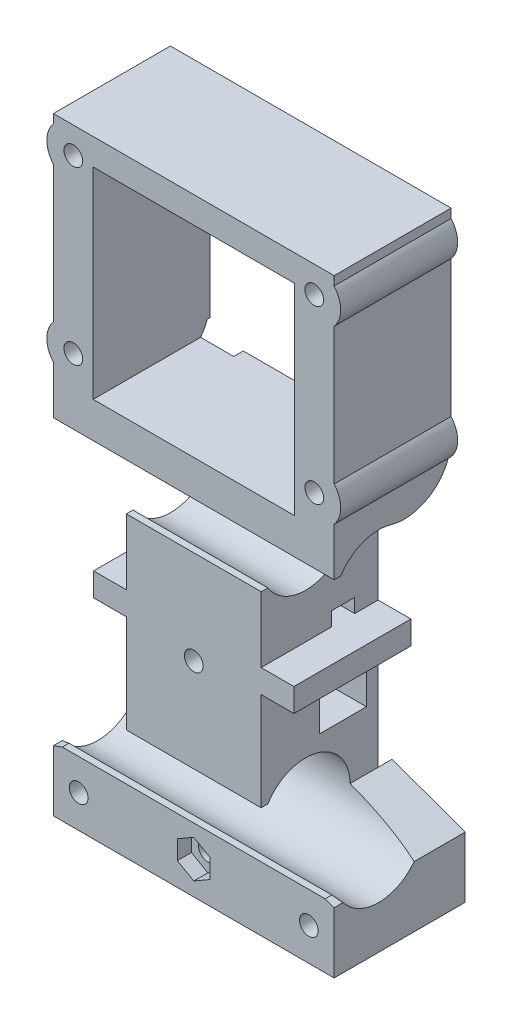
SolidWorks part; units mm, degrees
material "ABS"
ref_plane "Спереди" through (0, 0, 0) normal (0, 0, 1) x (1, 0, 0)
ref_plane "Сверху" through (0, 0, 0) normal (0, 1, 0) x (1, 0, 0)
ref_plane "Справа" through (0, 0, 0) normal (1, 0, 0) x (0, 0, -1)
sketch "Эскиз1" plane through (0, 0, 0) normal (0, 0, 1) x (1, 0, 0)
  line L1 (30, -65) -> (-30, -65)
  line L2 (30, -65) -> (30, 65)
  line L3 (30, 65) -> (-30, 65)
  line L4 (-30, -65) -> (-30, 65)
  line L5 (30, -65) -> (-30, 65) construction
  line L6 (30, 65) -> (-30, -65) construction
  point P0 (0, 0)
  dimension "D1" = 60
  dimension "D2" = 130
extrude "Бобышка-Вытянуть1" add sketch "Эскиз1" along normal blind 25
sketch "Эскиз2" plane through (0, 0, 0) normal (0, 0, -1) x (-1, 0, 0)
  line L0 (-30, 3.7) -> (-14.4, 3.7)
  line L1 (21.5, 16.35) -> (-21.5, 16.35)
  line L2 (21.5, 16.35) -> (21.5, 59.35)
  line L3 (21.5, 59.35) -> (-21.5, 59.35)
  line L4 (-21.5, 16.35) -> (-21.5, 59.35)
  line L5 (21.5, 16.35) -> (-21.5, 59.35) construction
  line L6 (21.5, 59.35) -> (-21.5, 16.35) construction
  line L7 (-30, -65) -> (-30, 65) construction
  line L8 (-14.4, -5.8) -> (-14.4, 13.2) construction
  line L9 (-14.4, 3.7) -> (-14.4, -46.3)
  line L10 (-14.4, -36.8) -> (-14.4, -55.8) construction
  line L11 (-14.4, -46.3) -> (-30, -52)
  line L12 (-30, -52) -> (-30, 3.7)
  line L13 (14.4, -46.3) -> (30, -52)
  line L14 (0, 16.35) -> (0, -65) construction
  line L15 (30, -65) -> (-30, -65) construction
  line L16 (14.4, 3.7) -> (14.4, -46.3)
  line L17 (30, 3.7) -> (14.4, 3.7)
  line L18 (30, -52) -> (30, 3.7)
  line L19 (-30, -65) -> (-30, 15) construction
  point P0 (0, 37.85)
  dimension "D1" = 43
  dimension "D3" = 13
extrude "Вырез-Вытянуть1" cut sketch "Эскиз2" against normal through all
sketch "Эскиз3" plane through (-30, 0, 0) normal (-1, 0, 0) x (0, 0, 1)
  line L0 (15.5, -5.8) -> (15.5, -36.9) construction
  line L1 (23.5777, 8.7) -> (25, 8.7)
  line L2 (6, -29.85) -> (25, -29.85) construction
  line L3 (6, -29.85) -> (6, -12.85) construction
  line L4 (6, -12.85) -> (25, -12.85) construction
  line L5 (25, -29.85) -> (25, -12.85) construction
  line L6 (6, -29.85) -> (25, -12.85) construction
  line L7 (6, -12.85) -> (25, -29.85) construction
  line L8 (2.5, -33.85) -> (12.5, -33.85)
  line L9 (2.5, -33.85) -> (2.5, -25.85)
  line L10 (2.5, -25.85) -> (12.5, -25.85)
  line L11 (12.5, -33.85) -> (12.5, -25.85)
  line L12 (2.5, -33.85) -> (12.5, -25.85) construction
  line L13 (2.5, -25.85) -> (12.5, -33.85) construction
  line L14 (25, 3.7) -> (25, 65) construction
  line L15 (25, 8.7) -> (25, 3.7)
  line L16 (25, -46.3) -> (25, 3.7) construction
  line L17 (25, -1.3) -> (23.5777, -1.3)
  line L18 (25, 8.7) -> (25, 3.7)
  line L19 (25, 3.7) -> (25, -1.3)
  line L20 (25, -1.3) -> (25, 3.7)
  line L21 (23.5777, -41.3) -> (25, -41.3)
  line L22 (25, -41.3) -> (25, -46.3)
  line L23 (25, -46.3) -> (25, -51.3)
  line L24 (25, -65) -> (25, -52) construction
  line L25 (25, -51.3) -> (23.5777, -51.3)
  line L26 (25, -65) -> (25, 15) construction
  arc A0 (23.5777, -41.3) -> (23.5777, -51.3) centre (15.5, -46.3) ccw
  arc A1 (23.5777, 8.7) -> (23.5777, -1.3) centre (15.5, 3.7) ccw
  circle A2 centre (15.5, 3.7) radius 9.5 construction
  circle A3 centre (15.5, -46.3) radius 9.4 construction
  point P4 (25, -46.3)
  point P13 (15.5, -21.35)
  point P18 (7.5, -29.85)
  point P34 (25, 3.7)
  line M2 (25, -52) -> (0, -52)
  dimension "D1" = 19
  dimension "D2" = 17
  dimension "D3" = 10
  dimension "D4" = 8
  dimension "D5" = 5
  dimension "D6" = 17.5
extrude "Вырез-Вытянуть2" cut sketch "Эскиз3" against normal through all contours L1 A1 L17 L19 L15 | L21 A0 L25 L23 L22 M2 | L8 L11 L10 L9 | A0 M2 region at (-30, 3.7, 15.6446) region at (-30, -29.85, 7.5) region at (-30, -45.1188, 15.6682) region at (-30, -53.5495, 15.5)
fillet "Скругление1" radius 20 2 edges at (-22.2, 3.7, 0) (22.2, 3.7, 0)
fillet "Скругление2" radius 10 2 edges at (-22.2, 3.7, 6) (22.2, 3.7, 6)
sketch "Эскиз4" plane through (0, 0, 0) normal (0, 0, -1) x (-1, 0, 0)
  line L0 (0, -1.3) -> (0, -41.3) construction
  line L1 (-14.4, -1.3) -> (14.4, -1.3) construction
  line L2 (-14.4, -41.3) -> (14.4, -41.3) construction
  line L3 (-30, 8.7) -> (30, 8.7) construction
  line L4 (30, 12.4083) -> (30, 22.4083) construction
  line L5 (21.5, 59.35) -> (-21.5, 59.35) construction
  circle A0 centre (-24.6, -58) radius 2
  circle A1 centre (24.6, -58) radius 2
  circle A2 centre (0, -21.3) radius 2
  circle A3 centre (-25.75, 22.7) radius 2
  circle A4 centre (25.75, 22.7) radius 2
  circle A5 centre (-24.6, -58) radius 2 construction
  circle A6 centre (25.75, 59.35) radius 2
  circle A7 centre (-25.75, 59.35) radius 2
  dimension "D1" = 14
  dimension "D2" = 4.25
extrude "Вырез-Вытянуть3" cut sketch "Эскиз4" against normal through all
sketch "Эскиз5" plane through (0, 0, 0) normal (0, 0, -1) x (-1, 0, 0)
  circle A0 centre (25.75, 22.7) radius 4.25
  circle A1 centre (-25.75, 22.7) radius 4.25
  circle A2 centre (-25.75, 22.7) radius 2
  circle A3 centre (25.75, 22.7) radius 2
  circle A4 centre (0, -21.3) radius 2 construction
  dimension "D1" = 8.5
extrude "Бобышка-Вытянуть2" add sketch "Эскиз5" against normal through all
sketch "Эскиз6" plane through (0, 0, 0) normal (0, 0, -1) x (-1, 0, 0)
  line L0 (-30, 65) -> (30, 65) construction
  line L1 (-21.5, 26.4229) -> (-21.5, 18.9771)
  line L2 (21.5, 59.35) -> (20.1, 59.35)
  line L3 (21.5, 59.35) -> (21.5, 55.6271)
  line L5 (-21.5, 59.35) -> (-21.5, 55.6271)
  line L7 (-21.5, 59.35) -> (-21.5, 22.4083) construction
  line L8 (-20.1, 59.35) -> (-21.5, 59.35)
  line L9 (21.5, 26.4229) -> (21.5, 18.9771)
  arc A0 (-20.1, 59.35) -> (-21.5, 55.6271) centre (-25.75, 59.35) ccw
  arc A1 (21.5, 55.6271) -> (20.1, 59.35) centre (25.75, 59.35) ccw
  arc A2 (21.5, 18.9771) -> (21.5, 26.4229) centre (25.75, 22.7) ccw
  arc A3 (-21.5, 26.4229) -> (-21.5, 18.9771) centre (-25.75, 22.7) ccw
  circle A4 centre (-25.75, 59.35) radius 2
  circle A5 centre (-25.75, 22.7) radius 2
  circle A6 centre (25.75, 59.35) radius 2
  circle A7 centre (25.75, 22.7) radius 2
  circle A8 centre (25.75, 22.7) radius 2 construction
extrude "Бобышка-Вытянуть3" add sketch "Эскиз6" against normal up to surface (25 mm away) up to face at (0, 37.85, 25)
sketch "Эскиз7" plane through (0, 0, 0) normal (0, 0, -1) x (-1, 0, 0)
  line L0 (30, -52) -> (30, -65) construction
  line L1 (0, -17.2585) -> (-3.5, -19.2793)
  line L2 (-3.5, -19.2793) -> (-3.5, -23.3207)
  line L3 (-3.5, -23.3207) -> (0, -25.3415)
  line L4 (0, -25.3415) -> (3.5, -23.3207)
  line L5 (3.5, -23.3207) -> (3.5, -19.2793)
  line L6 (3.5, -19.2793) -> (0, -17.2585)
  line L7 (-24.6, -53.9585) -> (-28.1, -55.9793)
  line L8 (-28.1, -55.9793) -> (-28.1, -60.0207)
  line L9 (-28.1, -60.0207) -> (-24.6, -62.0415)
  line L10 (-24.6, -62.0415) -> (-21.1, -60.0207)
  line L11 (-21.1, -60.0207) -> (-21.1, -55.9793)
  line L12 (-21.1, -55.9793) -> (-24.6, -53.9585)
  line L13 (24.6, -53.9585) -> (21.1, -55.9793)
  line L14 (21.1, -55.9793) -> (21.1, -60.0207)
  line L15 (21.1, -60.0207) -> (24.6, -62.0415)
  line L16 (24.6, -62.0415) -> (28.1, -60.0207)
  line L17 (28.1, -60.0207) -> (28.1, -55.9793)
  line L18 (28.1, -55.9793) -> (24.6, -53.9585)
  circle A0 centre (0, -21.3) radius 3.5 construction
  circle A1 centre (-24.6, -58) radius 3.5 construction
  circle A2 centre (24.6, -58) radius 3.5 construction
  dimension "D1" = 7
extrude "Вырез-Вытянуть4" cut sketch "Эскиз7" against normal blind 5
sketch "Эскиз8" plane through (0, 0, 25) normal (0, 0, 1) x (1, 0, 0)
  circle A0 centre (0, -58) radius 2
  circle A1 centre (-24.6, -58) radius 2 construction
extrude "Вырез-Вытянуть5" cut sketch "Эскиз8" against normal blind 20
sketch "Эскиз9" plane through (0, 0, 25) normal (0, 0, 1) x (1, 0, 0)
  line L0 (30, -65) -> (30, 15) construction
  line L1 (0, -53.9585) -> (-3.5, -55.9793)
  line L2 (-3.5, -55.9793) -> (-3.5, -60.0207)
  line L3 (-3.5, -60.0207) -> (0, -62.0415)
  line L4 (0, -62.0415) -> (3.5, -60.0207)
  line L5 (3.5, -60.0207) -> (3.5, -55.9793)
  line L6 (3.5, -55.9793) -> (0, -53.9585)
  circle A0 centre (0, -58) radius 3.5 construction
  dimension "D1" = 7
extrude "Вырез-Вытянуть6" cut sketch "Эскиз9" against normal blind 3
sketch "Эскиз11" plane through (14.4, 0, 0) normal (1, 0, 0) x (0, 0, -1)
  line L0 (-12.5, -25.85) -> (-2.5, -33.85) construction
  line L1 (-7.5, -29.85) -> (-7.5, -12.85) construction
  line L3 (-5, -15.35) -> (-10, -15.35) construction
  line L4 (-5, -15.35) -> (-5, -12.85) construction
  line L5 (-5, -12.85) -> (-10, -12.85) construction
  line L6 (-10, -15.35) -> (-10, -12.85) construction
  line L7 (-5, -15.35) -> (-10, -12.85) construction
  line L8 (-5, -12.85) -> (-10, -15.35) construction
  line L9 (-4, -20.35) -> (-11, -20.35)
  line L10 (-4, -20.35) -> (-4, -15.35)
  line L11 (-4, -15.35) -> (-11, -15.35)
  line L12 (-11, -20.35) -> (-11, -15.35)
  line L13 (-4, -20.35) -> (-11, -15.35) construction
  line L14 (-4, -15.35) -> (-11, -20.35) construction
  point P10 (-7.5, -17.85)
  dimension "D1" = 2.5
  dimension "D2" = 5
  dimension "D3" = 17
  dimension "D4" = 7
  dimension "D5" = 5
extrude "Бобышка-Вытянуть5" add sketch "Эскиз11" along normal blind 7
sketch "Эскиз12" plane through (-14.4, 0, 0) normal (-1, 0, 0) x (0, 0, 1)
  line L1 (11, -15.35) -> (4, -15.35)
  line L2 (11, -15.35) -> (11, -20.35)
  line L3 (11, -20.35) -> (4, -20.35)
  line L4 (4, -15.35) -> (4, -20.35)
extrude "Бобышка-Вытянуть6" add sketch "Эскиз12" along normal blind 7
sketch "Эскиз13" plane through (0, 0, 4) normal (0, 0, -1) x (-1, 0, 0)
  line L1 (21.4, -15.35) -> (14.4, -15.35)
  line L2 (21.4, -15.35) -> (21.4, -20.35)
  line L3 (21.4, -20.35) -> (14.4, -20.35)
  line L4 (14.4, -15.35) -> (14.4, -20.35)
  line L5 (-14.4, -15.35) -> (-21.4, -15.35)
  line L6 (-14.4, -15.35) -> (-14.4, -20.35)
  line L7 (-14.4, -20.35) -> (-21.4, -20.35)
  line L8 (-21.4, -15.35) -> (-21.4, -20.35)
extrude "Бобышка-Вытянуть7" add sketch "Эскиз13" along normal up to surface (4 mm away) up to face at (-24.6, -58, 0)
sketch "Эскиз17" plane through (0, 0, 11) normal (0, 0, 1) x (1, 0, 0)
  line L1 (21.4, -15.35) -> (14.4, -15.35)
  line L2 (21.4, -15.35) -> (21.4, -20.35)
  line L3 (21.4, -20.35) -> (14.4, -20.35)
  line L4 (14.4, -15.35) -> (14.4, -20.35)
  line L5 (-14.4, -20.35) -> (-21.4, -20.35)
  line L6 (-14.4, -20.35) -> (-14.4, -15.35)
  line L7 (-14.4, -15.35) -> (-21.4, -15.35)
  line L8 (-21.4, -20.35) -> (-21.4, -15.35)
extrude "Бобышка-Вытянуть8" add sketch "Эскиз17" along normal up to surface (14 mm away) up to face at (-2, -21.3, 25)
sketch "Эскиз18" plane through (0, 0, 0) normal (0, 0, -1) x (-1, 0, 0)
  line L0 (-30, -52) -> (-14.4, -46.3)
  line L1 (-14.4, -46.3) -> (-14.4, -65)
  line L2 (30, -65) -> (-30, -65) construction
  line L3 (-14.4, -65) -> (-30, -65)
  line L4 (-30, -65) -> (-30, -52)
  line L5 (-28.1, -55.9793) -> (-24.6, -53.9585)
  line L6 (-24.6, -53.9585) -> (-21.1, -55.9793)
  line L7 (-21.1, -55.9793) -> (-21.1, -60.0207)
  line L8 (-21.1, -60.0207) -> (-24.6, -62.0415)
  line L9 (-24.6, -62.0415) -> (-28.1, -60.0207)
  line L10 (-28.1, -60.0207) -> (-28.1, -55.9793)
extrude "Бобышка-Вытянуть9" add sketch "Эскиз18" along normal blind 3
sketch "Эскиз19" plane through (-14.4, 0, 0) normal (-1, 0, 0) x (0, 0, 1)
  line L0 (2.5, -25.85) -> (12.5, -33.85) construction
  line L1 (25, -15.35) -> (0, -15.35) construction
  line L2 (10, -15.35) -> (5, -15.35)
  line L3 (7.5, -29.85) -> (7.5, -15.35) construction
  line L4 (25, -15.35) -> (0, -15.35) construction
  line L5 (10, -15.35) -> (10, -12.35)
  line L6 (10, -12.35) -> (5, -12.35)
  line L7 (5, -15.35) -> (5, -12.35)
  line L8 (10, -15.35) -> (5, -12.35) construction
  line L9 (10, -12.35) -> (5, -15.35) construction
  point P5 (7.5, -13.85)
  dimension "D1" = 3
  dimension "D2" = 5
extrude "Вырез-Вытянуть7" cut sketch "Эскиз19" against normal through all
sketch "Эскиз20" plane through (0, 0, 0) normal (0, 0, -1) x (-1, 0, 0)
  line L0 (0, -21.3) -> (0, 16.35) construction
  line L1 (-14.4, 16.35) -> (14.4, 16.35) construction
  line L2 (-14.4, -12.35) -> (14.4, -12.35) construction
  line L3 (7.5, -7.35) -> (-7.5, -7.35)
  line L4 (7.5, -7.35) -> (7.5, -17.35)
  line L5 (7.5, -17.35) -> (-7.5, -17.35)
  line L6 (-7.5, -7.35) -> (-7.5, -17.35)
  line L7 (7.5, -7.35) -> (-7.5, -17.35) construction
  line L8 (7.5, -17.35) -> (-7.5, -7.35) construction
  point P5 (0, -12.35)
  dimension "D1" = 10
  dimension "D2" = 15
extrude "Вырез-Вытянуть8" cut sketch "Эскиз20" against normal blind 13
